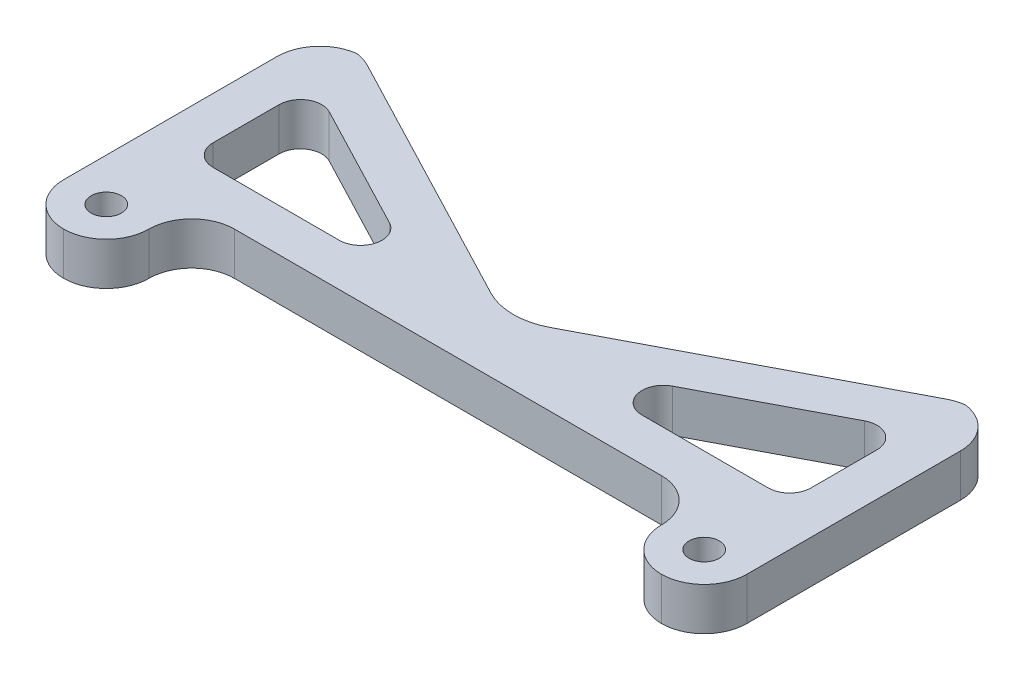
SolidWorks part; units mm, degrees
material "Custom Plastic"
ref_plane "Front Plane" through (0, 0, 0) normal (0, 0, 1) x (1, 0, 0)
ref_plane "Top Plane" through (0, 0, 0) normal (0, 1, 0) x (1, 0, 0)
ref_plane "Right Plane" through (0, 0, 0) normal (1, 0, 0) x (0, 0, -1)
sketch "Sketch1" plane through (0, 0, 0) normal (0, 1, 0) x (1, 0, 0)
  line L1 (-50.8, -34.925) -> (50.8, -34.925)
  line L2 (-50.8, -34.925) -> (-50.8, 34.925)
  line L3 (-50.8, 34.925) -> (50.8, 34.925)
  line L4 (50.8, -34.925) -> (50.8, 34.925)
  line L5 (-50.8, -34.925) -> (50.8, 34.925) construction
  line L6 (-50.8, 34.925) -> (50.8, -34.925) construction
  point P0 (0, 0)
  dimension "D1" = 101.6
  dimension "D2" = 69.85
extrude "Base" add sketch "Sketch1" along normal blind 6.35
sketch "Sketch2" plane through (0, 6.35, 0) normal (0, 1, 0) x (1, 0, 0)
  line L0 (-44.45, 34.925) -> (0, 11.6802)
  line L1 (50.8, 34.925) -> (-50.8, 34.925) construction
  line L2 (0, 11.6802) -> (44.45, 34.925)
  line L3 (-44.45, 34.925) -> (44.45, 34.925)
  line L4 (0, 0) -> (0, 34.925) construction
  circle A0 centre (0, 20.6375) radius 7.9375 construction
  dimension "D1" = 15.875
  dimension "D2" = 88.9
  dimension "D3" = 14.2875
extrude "Tube notch" cut sketch "Sketch2" against normal through all
sketch "Sketch3" plane through (0, 6.35, 0) normal (0, 1, 0) x (1, 0, 0)
  line L1 (0, 0) -> (0, -34.925) construction
  line L2 (-44.45, -3.175) -> (44.45, -3.175) construction
  line L3 (-44.45, -3.175) -> (-44.45, -28.575) construction
  line L4 (-44.45, -28.575) -> (44.45, -28.575) construction
  line L5 (44.45, -3.175) -> (44.45, -28.575) construction
  line L6 (-50.8, -34.925) -> (50.8, -34.925) construction
  line L7 (-50.8, 3.175) -> (50.8, 3.175) construction
  line L8 (-50.8, 34.925) -> (-50.8, -34.925) construction
  line L9 (50.8, -34.925) -> (50.8, 34.925) construction
  point P9 (0, -3.175)
  dimension "D1" = 88.9
  dimension "D2" = 6.35
  dimension "D3" = 25.4
  dimension "D4" = 6.35
hole_wizard "Mounting holes" positions "Sketch5" profile "Sketch4" hole size "#8" standard "ANSI Inch" end condition through all
sketch "Sketch5" plane through (0, 6.35, 0) normal (0, 1, 0) x (1, 0, 0)
  point P0 (-44.45, -3.175)
  point P9 (44.45, -3.175)
sketch "Sketch4" plane through (-44.45, 6.35, 3.175) normal (1, 0, 0) x (0, 0, 1)
  line L0 (0, 0) -> (0, 6.35)
  line L1 (0, 6.35) -> (2.2479, 6.35)
  line L2 (2.2479, 6.35) -> (2.2479, 0)
  line L5 (2.2479, 0) -> (0, 0)
  line L11 (0, -6.35) -> (0, 107.95) construction
  dimension "Thru Hole Dia." = 4.4958
  dimension "Thru Hole Depth" = 6.35
sketch "Sketch8" plane through (0, 6.35, 0) normal (0, 1, 0) x (1, 0, 0)
  line L0 (-50.8, -34.925) -> (50.8, -34.925) construction
  line L1 (-38.1, -34.925) -> (38.1, -34.925)
  line L2 (-38.1, -34.925) -> (-38.1, 3.175)
  line L3 (-38.1, 3.175) -> (38.1, 3.175)
  line L4 (38.1, -34.925) -> (38.1, 3.175)
  line L5 (-50.8, -9.525) -> (-38.1, -9.525)
  line L6 (-50.8, 34.925) -> (-50.8, -34.925) construction
  line L8 (38.1, -9.525) -> (50.8, -9.525)
  line L9 (50.8, -34.925) -> (50.8, 34.925) construction
  line L10 (50.8, -9.525) -> (50.8, -34.925)
  line L11 (50.8, -34.925) -> (38.1, -34.925)
  line L12 (-38.1, -34.925) -> (-50.8, -34.925)
  line L13 (-50.8, -34.925) -> (-50.8, -9.525)
  circle A0 centre (-44.45, -3.175) radius 2.2479 construction
  point P6 (0, 3.175)
  line M5 (50.8, -34.925) -> (50.8, 34.925)
  line M10 (-50.8, 34.925) -> (-50.8, -34.925)
  line M11 (-50.8, -34.925) -> (50.8, -34.925)
  dimension "D3" = 6.35
  dimension "D1" = 38.1
  dimension "D2" = 76.2
extrude "Wheel cutout" cut sketch "Sketch8" against normal through all contours L5 L2 M10 M11 | L4 L3 L2 M11 | L8 L4 M11 M5 region at (0, 6.35, 15.875) region at (-44.45, 6.35, 22.225) region at (44.45, 6.35, 22.225)
fillet "Fillet1" radius 6.35 10 edges at (-44.45, 3.175, -34.925) (44.45, 3.175, -34.925) (50.8, 3.175, -34.925) (38.1, 3.175, -3.175) (-38.1, 3.175, -3.175) (-50.8, 3.175, -34.925) (50.8, 3.175, 9.525) (38.1, 3.175, 9.525) (-50.8, 3.175, 9.525) (-38.1, 3.175, 9.525)
fillet "Fillet2" radius 9.525 1 edges at (0, 3.175, -11.6802)
sketch "Sketch9" plane through (0, 6.35, 0) normal (0, 1, 0) x (1, 0, 0)
  line L0 (-44.45, 9.525) -> (-44.45, 27.7591)
  line L1 (-44.45, 27.7591) -> (-9.5817, 9.525)
  line L2 (9.5817, 9.525) -> (44.45, 27.7591)
  line L3 (44.45, 27.7591) -> (44.45, 9.525)
  line L4 (44.45, 9.525) -> (9.5817, 9.525)
  line L5 (-43.0675, 34.202) -> (-4.4139, 13.9884) construction
  line L6 (-50.8, 28.575) -> (-50.8, -3.175) construction
  line L7 (31.75, 3.175) -> (-31.75, 3.175) construction
  line L10 (-9.5817, 9.525) -> (-44.45, 9.525)
  line L11 (4.4139, 13.9884) -> (43.0675, 34.202) construction
  line L12 (50.8, -3.175) -> (50.8, 28.575) construction
  dimension "D1" = 6.35
  dimension "D2" = 6.35
  dimension "D3" = 6.35
  dimension "D5" = 6.35
extrude "Cut-Extrude1" cut sketch "Sketch9" against normal through all
fillet "Fillet3" radius 3.175 6 edges at (-44.45, 3.175, -9.525) (44.45, 3.175, -9.525) (44.45, 3.175, -27.7591) (-44.45, 3.175, -27.7591) (9.5817, 3.175, -9.525) (-9.5817, 3.175, -9.525)
equation "\"MAT_THICKNESS\"=0.1"
